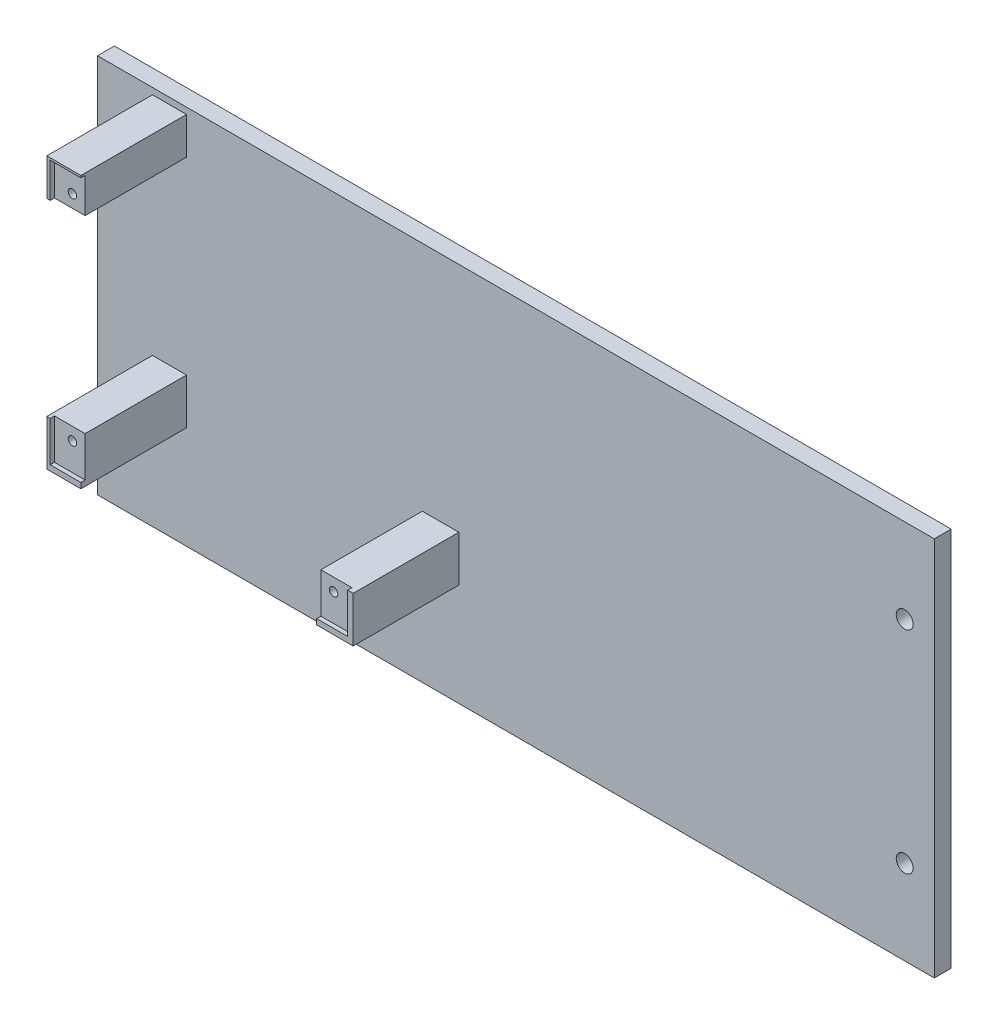
SolidWorks part; units mm, degrees
ref_plane "Front Plane" through (0, 0, 0) normal (0, 0, 1) x (1, 0, 0)
ref_plane "Top Plane" through (0, 0, 0) normal (0, 1, 0) x (1, 0, 0)
ref_plane "Right Plane" through (0, 0, 0) normal (1, 0, 0) x (0, 0, -1)
sketch "Sketch1" plane through (0, 0, 0) normal (0, 0, 1) x (1, 0, 0)
  line L1 (0, 0) -> (198, 0)
  line L2 (0, 0) -> (0, 90)
  line L3 (0, 90) -> (198, 90)
  line L4 (198, 0) -> (198, 90)
  dimension "D1" = 90
  dimension "D2" = 198
extrude "Boss-Extrude1" add sketch "Sketch1" along normal blind 4
sketch "Sketch3" plane through (0, 0, 0) normal (0, 0, -1) x (-1, 0, 0)
  circle A0 centre (-191, 20) radius 2
  circle A1 centre (-191, 70) radius 2
  circle A2 centre (-7, 20) radius 2
  circle A3 centre (-7, 70) radius 2
  dimension "D1" = 4
  dimension "D2" = 4
  dimension "D3" = 4
  dimension "D4" = 4
extrude "Cut-Extrude1" cut sketch "Sketch3" against normal blind 10
sketch "Sketch4" plane through (0, 0, 4) normal (0, 0, 1) x (1, 0, 0)
  line L0 (13.8, 79.7502) -> (13.8, 88.016)
  line L1 (21.0527, 88.5) -> (13, 88.5)
  line L2 (13, 88.5) -> (13, 79.7502)
  line L3 (15.0527, 79.7502) -> (21.0527, 79.7502)
  line L4 (21.0527, 85.7502) -> (21.0527, 79.7502)
  line L7 (13.8, 88.016) -> (21.0527, 88.016)
  line L9 (15.0527, 79.7502) -> (13, 79.7502)
  line L11 (15.0527, 35.092) -> (13, 35.092)
  line L12 (21.0527, 35.092) -> (15.0527, 35.092)
  line L13 (21.0527, 35.092) -> (21.0527, 28.3141)
  line L14 (21.0527, 85.7502) -> (21.0527, 88.5)
  line L16 (21.0527, 25.58) -> (13.8, 25.58)
  line L17 (13.8, 25.58) -> (13.8, 35.092)
  line L18 (82.8556, 35.092) -> (85.5, 35.092)
  line L19 (13, 35.092) -> (13, 24.28)
  line L20 (13, 24.28) -> (21.0527, 24.28)
  line L21 (21.0527, 24.28) -> (21.0527, 28.3141)
  line L22 (76.8556, 35.092) -> (82.8556, 35.092)
  line L23 (76.8556, 35.092) -> (76.8556, 29.092)
  line L26 (84.2, 35.092) -> (84.2, 25.58)
  line L27 (84.2, 25.58) -> (76.8556, 25.58)
  line L28 (85.5, 35.092) -> (85.5, 24.28)
  line L29 (85.5, 24.28) -> (76.8556, 24.28)
  line L30 (76.8556, 24.28) -> (76.8556, 29.092)
  circle A0 centre (79.8556, 32.092) radius 1
  circle A1 centre (18.0527, 32.092) radius 1
  circle A2 centre (18.0527, 82.7502) radius 1
  point P0 (0, 0)
  dimension "D1" = 3
  dimension "D2" = 3
  dimension "D3" = 3
  dimension "D4" = 3
  dimension "D5" = 3
  dimension "D6" = 3
extrude "Boss-Extrude3" add sketch "Sketch4" along normal blind 24 contours L4 L14 L7 L0 L9 L3 A2 | L16 L21 L13 L12 L11 L17 A1 | L30 L27 L26 L18 L22 L23 A0 | A1 | A2 | A0 region at (17.3917, 83.9457, 4) region at (17.3964, 30.2522, 4) region at (80.5595, 30.2533, 4) region at (79.8556, 32.092, 4) region at (18.0527, 32.092, 4) region at (18.0527, 82.7502, 4)
extrude "Boss-Extrude4" add sketch "Sketch4<4>" along normal blind 25 contours L7 L14 L1 L2 L9 L0 | L20 L21 L16 L17 L11 L19 | L30 L29 L28 L18 L26 L27 region at (13.4, 79.8691, 4) region at (13.6652, 30.336, 4) region at (84.85, 34.9536, 4)
sketch "Sketch4<4>" plane through (0, 0, 4) normal (0, 0, 1) x (1, 0, 0) same geometry as "Sketch4"
extrude "Cut-Extrude2" cut sketch "Sketch4<5>" along normal through all both and the other way through all contours A2 | A1 | A0 region at (79.8556, 32.092, 4) region at (18.0527, 32.092, 4) region at (18.0527, 82.7502, 4)
sketch "Sketch4<5>" plane through (0, 0, 4) normal (0, 0, 1) x (1, 0, 0) same geometry as "Sketch4"
